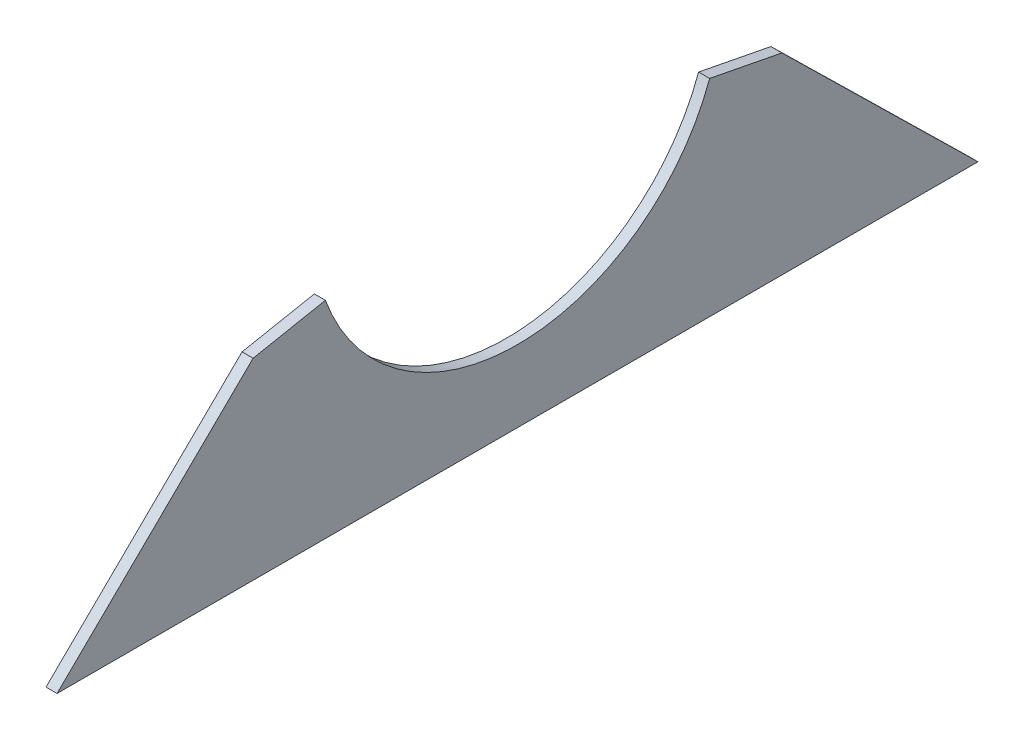
SolidWorks part; units mm, degrees
note: The reader was unsure of these and kept them because the rebuilt part matched: thickness of "Базовая кромка1", "Листовой металл3".
material "AISI 304"
ref_plane "Спереди" through (0, 0, 0) normal (0, 0, 1) x (1, 0, 0)
ref_plane "Сверху" through (0, 0, 0) normal (0, 1, 0) x (1, 0, 0)
ref_plane "Справа" through (0, 0, 0) normal (1, 0, 0) x (0, 0, -1)
sketch "Эскиз1" plane through (0, 0, 0) normal (1, 0, 0) x (0, 0, -1)
  line L0 (-111, 0) -> (111, 0) construction
  line L2 (250, -150) -> (-250, -150)
  line L4 (0, 0) -> (0, -150) construction
  line L5 (-250, -150) -> (-104.3059, -37.9642) construction
  line L6 (-104.3059, -37.9642) -> (0, 0) construction
  line L7 (104.3059, -37.9642) -> (250, -150) construction
  line L8 (0, 0) -> (104.3059, -37.9642) construction
  line L9 (-104.3059, -37.9642) -> (-143.571, -45.5966)
  line L10 (-143.571, -45.5966) -> (-250, -150)
  line L11 (143.571, -45.5966) -> (250, -150)
  line L12 (104.3059, -37.9642) -> (143.571, -45.5966)
  arc A0 (-104.3059, -37.9642) -> (104.3059, -37.9642) centre (0, 0) ccw
  dimension "D1" = 500
  dimension "D2" = 111
  dimension "D3" = 150
  dimension "D4" = 140
  dimension "D5" = 158
  dimension "D6" = 40
base flange "Базовая кромка1" sketch "Эскиз1" thickness 6 reverse thickness direction no parameters "D1"=4
sketch "Сгиб-Линии1" plane through (0, 0, 0) normal (0, 1, 0) x (1, 0, 0)
sketch "Граничная рамка1" plane through (0, 0, 0) normal (0, 1, 0) x (1, 0, 0)
sheet metal parameters "Листовой металл3" thickness 6 parameters "D1"=4
flat pattern "Развертка3" [suppressed]
sketch "Сгиб-Линии2" plane through (0, 0, 0) normal (0, 1, 0) x (1, 0, 0)
sketch "Граничная рамка2" [suppressed] plane through (0, 0, 0) normal (0, 1, 0) x (1, 0, 0)
